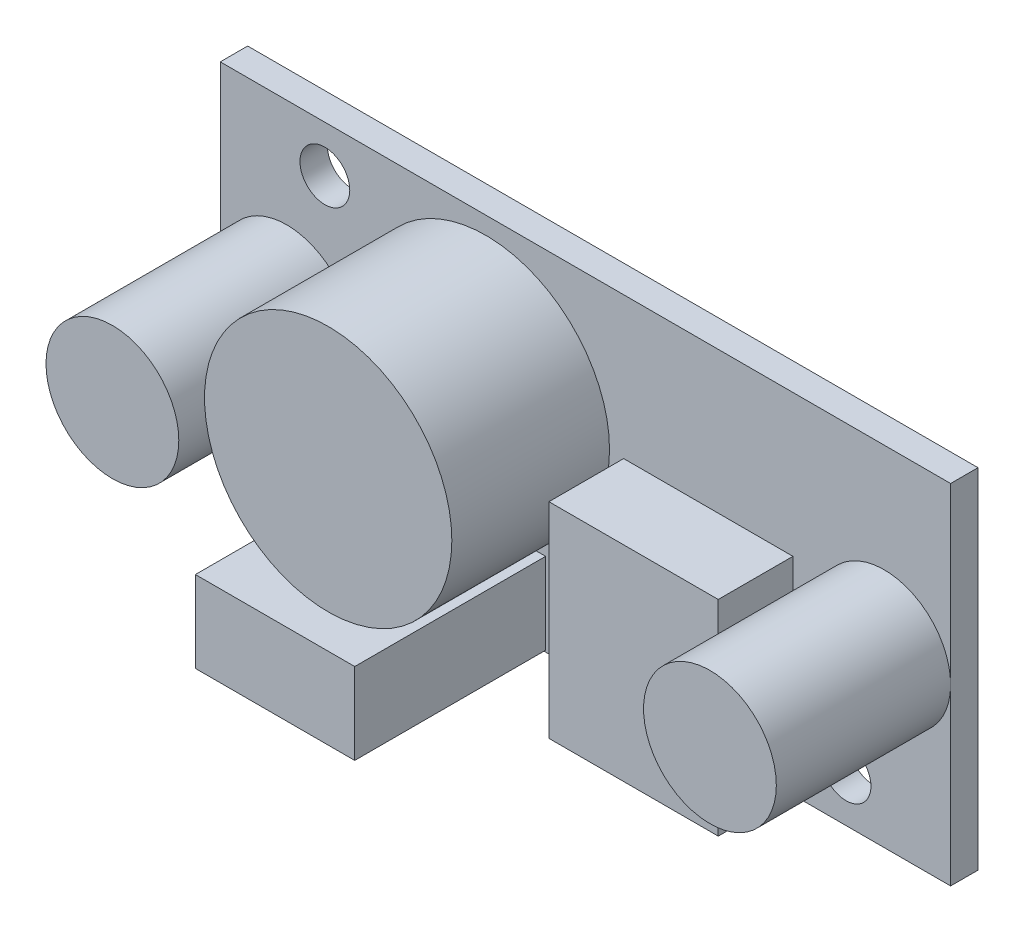
SolidWorks part; units mm, degrees
ref_plane "Спереди" through (0, 0, 0) normal (0, 0, 1) x (1, 0, 0)
ref_plane "Сверху" through (0, 0, 0) normal (0, 1, 0) x (1, 0, 0)
ref_plane "Справа" through (0, 0, 0) normal (1, 0, 0) x (0, 0, -1)
sketch "Эскиз1" plane through (0, 0, 0) normal (0, 0, 1) x (1, 0, 0)
  line L1 (-22, 10.5) -> (22, 10.5)
  line L2 (-22, 10.5) -> (-22, -10.5)
  line L3 (-22, -10.5) -> (22, -10.5)
  line L4 (22, 10.5) -> (22, -10.5)
  line L5 (-22, 10.5) -> (22, -10.5) construction
  line L6 (-22, -10.5) -> (22, 10.5) construction
  circle A0 centre (-15.7, 7.7) radius 1.5
  circle A1 centre (15.7, -7.7) radius 1.5
  point P0 (0, 0)
  point P12 (0, 0)
  dimension "D3" = 3
  dimension "D1" = 44
  dimension "D2" = 21
  dimension "D4" = 2.8
  dimension "D5" = 6.3
  dimension "D6" = 6.3
  dimension "D7" = 2.8
extrude "Плата основа" add sketch "Эскиз1" along normal blind 1.65
sketch "Эскиз2" plane through (0, 0, 1.65) normal (0, 0, 1) x (1, 0, 0)
  line L0 (-22, 10.5) -> (-22, -10.5) construction
  line L1 (-12, -5.5) -> (-2.4, -5.5)
  line L2 (-12, -5.5) -> (-12, -10.4)
  line L3 (-12, -10.4) -> (-2.4, -10.4)
  line L4 (-2.4, -5.5) -> (-2.4, -10.4)
  line L5 (-12, -5.5) -> (-2.4, -10.4) construction
  line L6 (-12, -10.4) -> (-2.4, -5.5) construction
  line L7 (2.3, 1.95) -> (12.5, 1.95)
  line L8 (2.3, 1.95) -> (2.3, -10.4)
  line L9 (2.3, -10.4) -> (12.5, -10.4)
  line L10 (12.5, 1.95) -> (12.5, -10.4)
  line L11 (2.3, 1.95) -> (12.5, -10.4) construction
  line L12 (2.3, -10.4) -> (12.5, 1.95) construction
  line L13 (-22, -10.5) -> (22, -10.5) construction
  line L15 (22, 10.5) -> (-22, 10.5) construction
  line L17 (22, -10.5) -> (22, 10.5) construction
  circle A0 centre (-18, 0) radius 4
  circle A1 centre (-6, 2) radius 7.45
  circle A2 centre (18, 0) radius 4
  point P4 (-7.2, -7.95)
  point P9 (7.4, -4.225)
  point P19 (-22, 0)
  point P22 (0, 0)
  line M16 (-22, -10.5) -> (22, -10.5)
  dimension "D1" = 8
  dimension "D2" = 14.9
  dimension "D3" = 9.6
  dimension "D4" = 4.9
  dimension "D5" = 10.2
  dimension "D6" = 12.35
  dimension "D8" = 8.5
  dimension "D9" = 16
  dimension "D10" = 10
  dimension "D11" = 9.5
  dimension "D12" = 0.1
  dimension "D7" = 2
extrude "Конденсаторы" add sketch "Эскиз2" along normal blind 10.5 contours A0 | A2 region at (-18, 0, 1.65) region at (18, 0, 1.65)
extrude "Регулятор" add sketch "Эскиз2<3>" along normal blind 11.5 contours L4 L1 L2 M16 region at (-7.2, -7.95, 1.65)
sketch "Эскиз2<3>" plane through (0, 0, 1.65) normal (0, 0, 1) x (1, 0, 0) same geometry as "Эскиз2"
extrude "Катушка индуктивности" add sketch "Эскиз2<4>" along normal blind 9.5 contours A1 region at (-6, 2, 1.65)
sketch "Эскиз2<4>" plane through (0, 0, 1.65) normal (0, 0, 1) x (1, 0, 0) same geometry as "Эскиз2"
extrude "Микросхема" add sketch "Эскиз2<5>" along normal blind 4.5 contours L10 L7 L8 M16 region at (7.4, -4.225, 1.65)
sketch "Эскиз2<5>" plane through (0, 0, 1.65) normal (0, 0, 1) x (1, 0, 0) same geometry as "Эскиз2"
